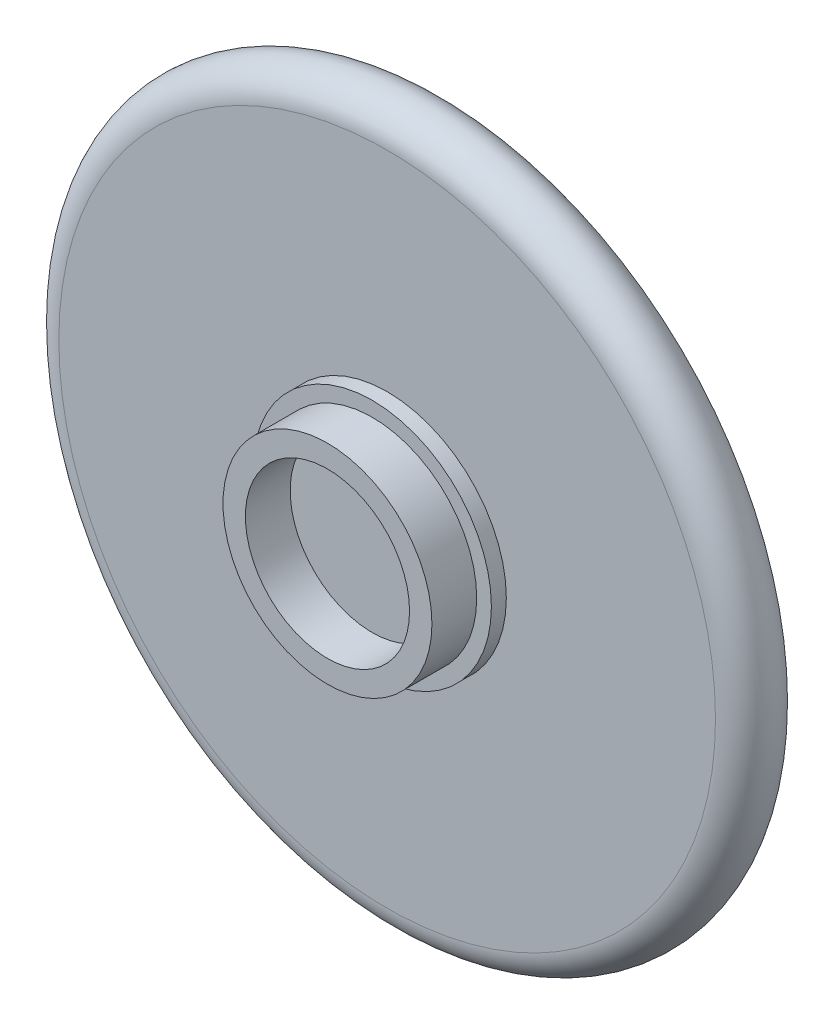
SolidWorks part; units mm, degrees
ref_plane "Front Plane" through (0, 0, 0) normal (0, 0, 1) x (1, 0, 0)
ref_plane "Top Plane" through (0, 0, 0) normal (0, 1, 0) x (1, 0, 0)
ref_plane "Right Plane" through (0, 0, 0) normal (1, 0, 0) x (0, 0, -1)
sketch "Sketch1" plane through (0, 0, 0) normal (0, 0, 1) x (1, 0, 0)
  circle A0 centre (0, 0) radius 12
  dimension "D1" = 24
extrude "Boss-Extrude1" add sketch "Sketch1" along normal blind 2
sketch "Sketch2" plane through (0, 0, 2) normal (0, 0, 1) x (1, 0, 0)
  circle A0 centre (0, 0) radius 3.5
  circle A1 centre (0, 0) radius 2.75
  dimension "D1" = 7
  dimension "D2" = 5.5
extrude "Boss-Extrude2" add sketch "Sketch2" along normal blind 2
fillet "Fillet1" 2 edges at (12, 0, 2) (12, 0, 0) type full round first side face at (3.5, 0, 2) second side face at (12, 0, 0) middle face at (12, 0, 2)
sketch "Sketch3" plane through (0, 0, 0) normal (0, 0, -1) x (-1, 0, 0)
  circle A0 centre (0, 0) radius 2.5
  circle A1 centre (-4.5841, -1.9966) radius 1.5
  circle A2 centre (4.6031, -1.9522) radius 1.5172
  circle A3 centre (0, 5) radius 1.5
  circle A4 centre (0, 0) radius 4.9
  circle A5 centre (0, 0) radius 5.1
  spline S0 degree 3 poles (-6.0621, -2.2524) (-6.0265, -2.751) (-8.7599, -2.6879) (-5.6816, -3.687) (-5.6447, -3.0572) knots 0 0 0 0 0.44428 1 1 1 1
  spline S1 degree 3 poles (6.0904, -2.2524) (6.685, -1.6246) (7.2896, -4.5846) (6.0715, -2.3606) (5.7842, -2.9046) knots 0 0 0 0 0.568767 1 1 1 1
  spline S2 degree 3 poles (-0.5545, 6.3938) (-1.4376, 6.095) (0.0026, 8.0798) (-0.0019, 7.1935) (-0.4423, 6.8682) (0.1353, 6.4939) knots 0 0 0 0 0.556265 0.56197 1 1 1 1
extrude "Boss-Extrude3" add sketch "Sketch3" along normal blind 1 contours S2 A3 | A5 A3 | A3 A4 | A3 A5 A1 A4 | A3 A5 A4 | A2 A5 A3 A4 | A2 A4 | A2 A5 A4 | A1 A5 A2 A4 | A5 A1 | A1 S0 | A1 A5 A4 | A1 A4 | A0 | S1 A2 A5 | S1 A2 region at (0, 0, 0) region at (5.1787, -2.2555, 0) region at (6.3845, -2.962, 0) region at (4.2111, 2.7591, 0) region at (4.5155, -1.9667, 0) region at (3.7435, -3.3344, 0) region at (3.9147, -1.705, 0) region at (0, 4.9252, 0) region at (0, 5.6486, 0) region at (-5.2059, -2.2077, 0) region at (-4.5327, -1.9223, 0) region at (0, 4.2698, 0) region at (0.3746, 6.886, 0) region at (-4.0486, 2.9934, 0) region at (-3.9234, -1.6639, 0) region at (-6.4526, -2.6597, 0)
sketch "Sketch4" plane through (0, 0, 2) normal (0, 0, 1) x (1, 0, 0)
  circle A0 centre (0, 0) radius 3.9922
extrude "Boss-Extrude4" add sketch "Sketch4" along normal blind 0.5 contours A0
